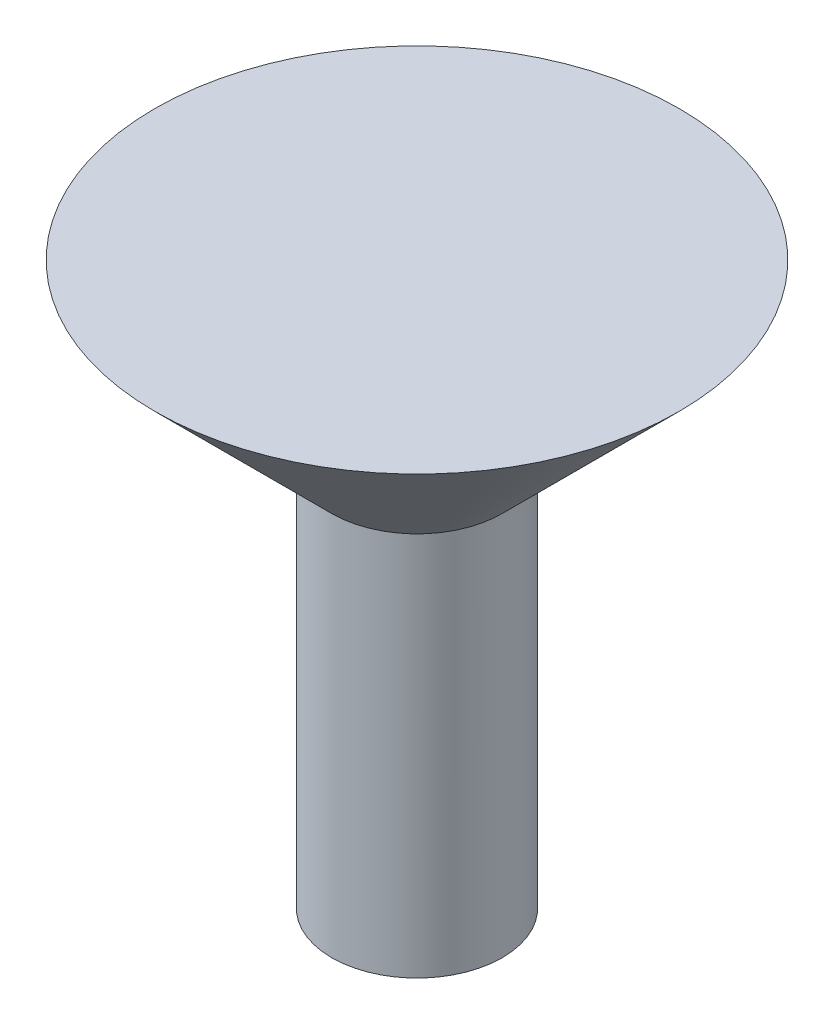
SolidWorks part; units mm, degrees
ref_plane "Front Plane" through (0, 0, 0) normal (0, 0, 1) x (1, 0, 0)
ref_plane "Top Plane" through (0, 0, 0) normal (0, 1, 0) x (1, 0, 0)
ref_plane "Right Plane" through (0, 0, 0) normal (1, 0, 0) x (0, 0, -1)
sketch "Sketch1" plane through (0, 0, 0) normal (0, 0, 1) x (1, 0, 0)
  line L0 (0, 2.5) -> (0, -2.5) construction
  line L1 (0, -2.5) -> (-2.5, -2.5) construction
  line L2 (-2.5, -2.5) -> (-7.5, 2.5) construction
  line L3 (-7.5, 2.5) -> (0, 2.5) construction
  line L4 (-0.2, 2.3) -> (-0.2, -2.3)
  line L5 (-0.2, -2.3) -> (-2.4172, -2.3)
  line L6 (-2.4172, -2.3) -> (-7.0172, 2.3)
  line L7 (-7.0172, 2.3) -> (-0.2, 2.3)
  dimension "D1" = 5
  dimension "D2" = 7.5
  dimension "D3" = 2.5
  dimension "D4" = 0.2
revolve "Revolve1" add sketch "Sketch1" angle 360 about L4
sketch "Sketch2" plane through (0, -2.3, 0) normal (0, -1, 0) x (1, 0, 0)
  circle A1 centre (-0.2, 0) radius 2.2172
  circle A2 centre (-0.2, 0) radius 2.2172
  dimension "D1" = 0
extrude "Boss-Extrude1" add sketch "Sketch2" along normal blind 10
sketch "Sketch3" plane through (0, -12.3, 0) normal (0, -1, 0) x (1, 0, 0)
  circle A0 centre (-0.2, 0) radius 1.55
  circle A1 centre (-0.2, 0) radius 2.2172 construction
  dimension "D1" = 3.1
extrude "Boss-Extrude2" add sketch "Sketch3" against normal blind 3
extrude "Cut-Extrude1" cut sketch "Sketch3<2>" against normal blind 5
sketch "Sketch3<2>" plane through (0, -12.3, 0) normal (0, -1, 0) x (1, 0, 0) same geometry as "Sketch3"
